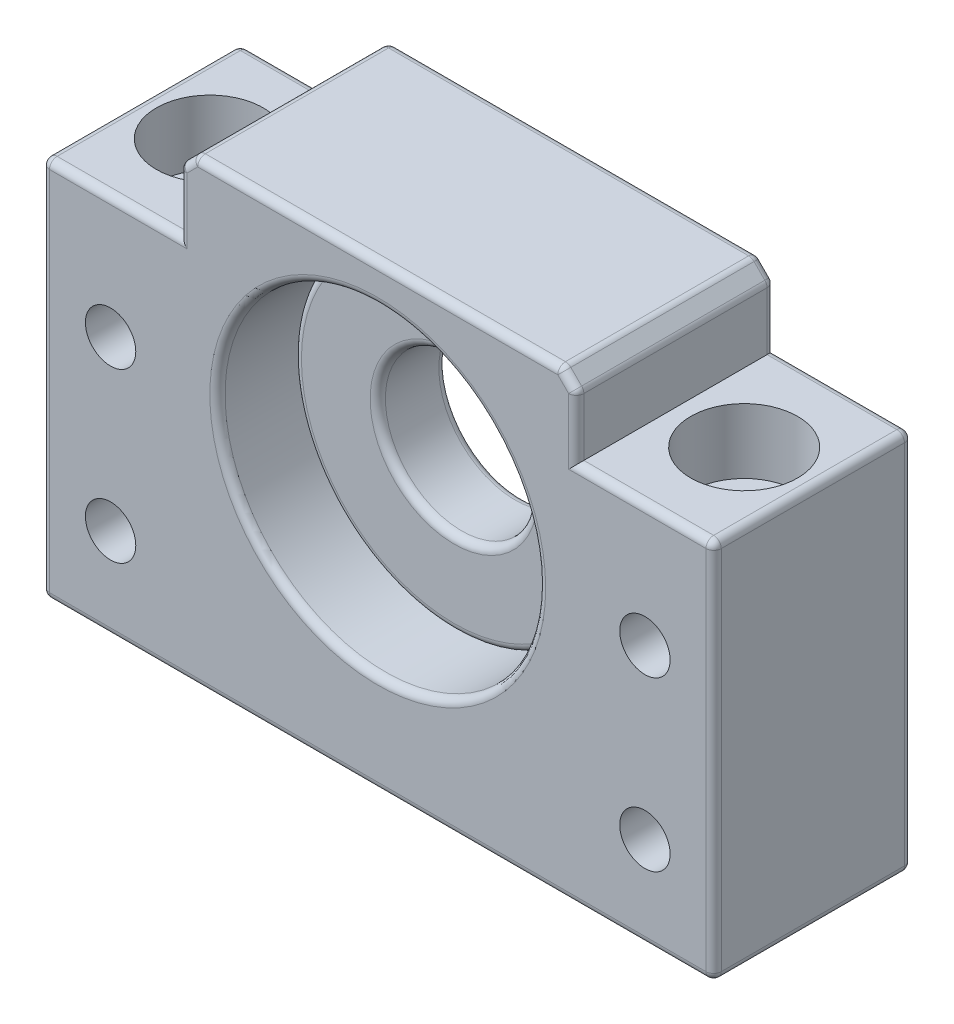
SolidWorks part; units mm, degrees
ref_plane "Front Plane" through (0, 0, 0) normal (0, 0, 1) x (1, 0, 0)
ref_plane "Top Plane" through (0, 0, 0) normal (0, 1, 0) x (1, 0, 0)
ref_plane "Right Plane" through (0, 0, 0) normal (1, 0, 0) x (0, 0, -1)
sketch "Sketch2" plane through (0, 0, 0) normal (0, 0, 1) x (1, 0, 0)
  line L0 (0, 0) -> (0, -34) construction
  line L3 (-44, 16) -> (-26, 16)
  line L4 (-44, 16) -> (-44, -34)
  line L5 (-44, -34) -> (44, -34)
  line L6 (44, 16) -> (44, -34)
  line L7 (-26, 26) -> (26, 26)
  line L8 (-26, 26) -> (-26, 16)
  line L9 (26, 26) -> (26, 16)
  line L10 (26, 16) -> (44, 16)
  line L11 (-44, 0) -> (44, 0) construction
  line L12 (0, 0) -> (0, 26) construction
  line L14 (-26, 16) -> (-26, 0) construction
  line L15 (26, 16) -> (26, 0) construction
  dimension "B" = 88
  dimension "h" = 34
  dimension "H1" = 50
  dimension "H2" = 60
  dimension "B1" = 52
extrude "Boss-Extrude1" add sketch "Sketch2" along normal blind 26
sketch "Sketch11" plane through (0, 0, 0) normal (0, 0, 1) x (1, 0, 0)
  line L0 (-35, 37.7108) -> (35, 37.7108) construction
  line L1 (0, 37.7108) -> (0, 0) construction
  line L2 (35, 37.7108) -> (35, 16) construction
  line L3 (-35, 37.7108) -> (-35, 16) construction
  line L4 (-26, 16) -> (-44, 16) construction
  line L5 (-35, 16) -> (-35, -34) construction
  line L6 (-44, -34) -> (44, -34) construction
  line L7 (44, 16) -> (26, 16) construction
  line L8 (35, 16) -> (35, -34) construction
  point P3 (0, 37.7108)
  dimension "P" = 70
sketch "Sketch12" plane through (0, 16, 0) normal (0, 1, 0) x (1, 0, 0)
  line L0 (-35, 0) -> (-35, -26) construction
  line L3 (-26, -26) -> (-44, -26) construction
  line L4 (35, 0) -> (35, -26) construction
  line L5 (44, -26) -> (26, -26) construction
  line L6 (-44, -13) -> (44, -13) construction
  line L9 (-44, -26) -> (-44, 0) construction
  line L10 (44, -26) -> (44, 0) construction
  circle A0 centre (-35, -13) radius 4.5
  circle A1 centre (35, -13) radius 4.5
  dimension "X" = 9
extrude "Cut-Extrude3" cut sketch "Sketch12" against normal blind 100
sketch "Sketch13" plane through (0, 0, 0) normal (0, 0, 1) x (1, 0, 0)
  line L0 (-35, 0) -> (35, 0) construction
  line L1 (-35, 16) -> (-35, -34) construction
  line L2 (35, 16) -> (35, -34) construction
  line L3 (-35, -22) -> (35, -22) construction
  line L4 (0, 0) -> (0, -22) construction
  line L5 (0, -22) -> (0, -34) construction
  line L6 (-44, -34) -> (44, -34) construction
  line L7 (0, 0) -> (0, 26) construction
  line L8 (26, 26) -> (-26, 26) construction
  circle A0 centre (-35, 0) radius 3.3
  circle A1 centre (-35, -22) radius 3.3
  circle A2 centre (35, -22) radius 3.3
  circle A3 centre (35, 0) radius 3.3
  circle A4 centre (0, 0) radius 21
  dimension "D1" = 42
  dimension "d2" = 6.6
  dimension "E" = 22
extrude "Cut-Extrude4" cut sketch "Sketch13" along normal blind 50
sketch "Sketch14" plane through (0, 16, 0) normal (0, 1, 0) x (1, 0, 0)
  circle A0 centre (-35, -13) radius 7
  circle A1 centre (35, -13) radius 7
  dimension "Y" = 14
extrude "Cut-Extrude5" cut sketch "Sketch14" against normal blind 8.5
sketch "Sketch16" plane through (0, 0, 0) normal (0, 0, 1) x (1, 0, 0)
  circle A0 centre (0, 0) radius 21
  circle A1 centre (0, 0) radius 10
  dimension "D1" = 42
  dimension "D2" = 20
extrude "Boss-Extrude3" add sketch "Sketch16" along normal blind 9 from offset 7 separate body
chamfer "Chamfer1" distance 2 angle 45 2 edges at (-26, 26, 13) (26, 26, 13)
fillet "Fillet1" radius 1 30 edges at (21, 0, 0) (21, 0, 26) (44, -34, 13) (-44, -34, 13) (-44, 16, 13) (44, 16, 13) (-35, 16, 26) (-35, 16, 0) (0, 26, 26) (0, 26, 0) (35, 16, 26) (35, 16, 0) (0, -34, 26) (0, -34, 0) (-44, -9, 26) (-44, -9, 0) (44, -9, 26) (44, -9, 0) (25, 25, 0) (26, 20, 0) (26, 20, 26) (25, 25, 26) (-26, 20, 0) (-25, 25, 0) (-26, 20, 26) (-25, 25, 26) (26, 24, 13) (24, 26, 13) (-26, 24, 13) (-24, 26, 13)
fillet "Fillet2" radius 1 4 edges at (10, 0, 16) (10, 0, 7) (21, 0, 7) (21, 0, 16)
equation "\"H\"=95.732"
equation "\"E\"=31.8321"
